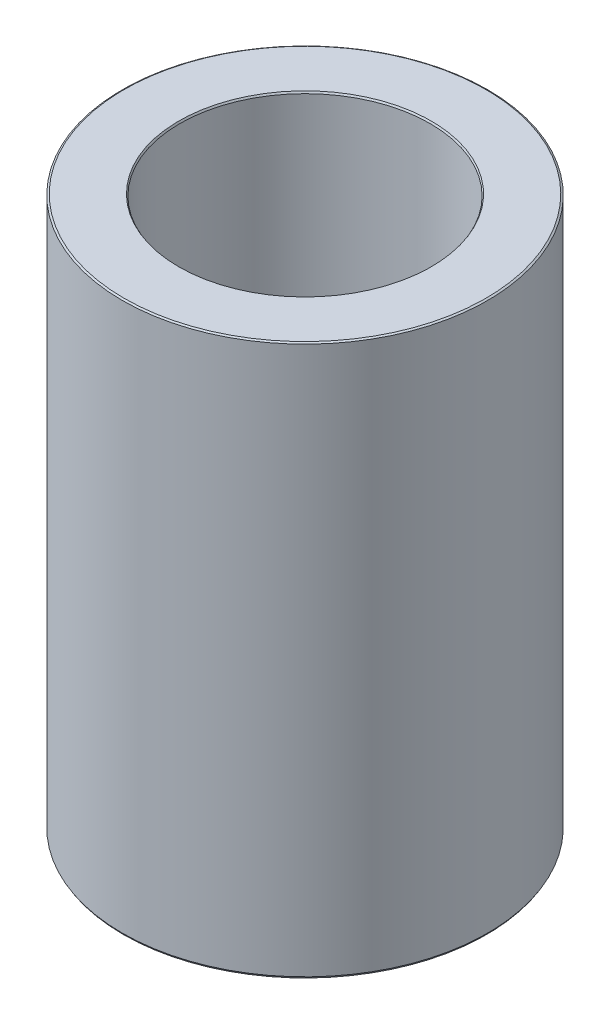
SolidWorks part; units mm, degrees
ref_plane "Front Plane" through (0, 0, 0) normal (0, 0, 1) x (1, 0, 0)
ref_plane "Top Plane" through (0, 0, 0) normal (0, 1, 0) x (1, 0, 0)
ref_plane "Right Plane" through (0, 0, 0) normal (1, 0, 0) x (0, 0, -1)
sketch "Sketch1" plane through (0, 0, 0) normal (0, 1, 0) x (1, 0, 0)
  circle A0 centre (0, 0) radius 50
  dimension "SLEEVE_OD" = 100
extrude "Boss-Extrude1" add sketch "Sketch1" along normal blind 150.78
sketch "Sketch2" plane through (0, 0, 0) normal (0, 1, 0) x (1, 0, 0)
  circle A0 centre (0, 0) radius 34.2984
  dimension "BORE_D" = 68.5969
extrude "Cut-Extrude1" cut sketch "Sketch2" along normal through all
chamfer "Chamfer1" distance 0.2755 angle 60 4 edges at (0, 150.78, 34.2984) (0, 0, 34.2984) (0, 0, 50) (0, 150.78, 50) first distance on face at (0, 150.78, 34.2984) first distance on face at (0, 0, 34.2984) first distance on face at (0, 150.78, 50)
